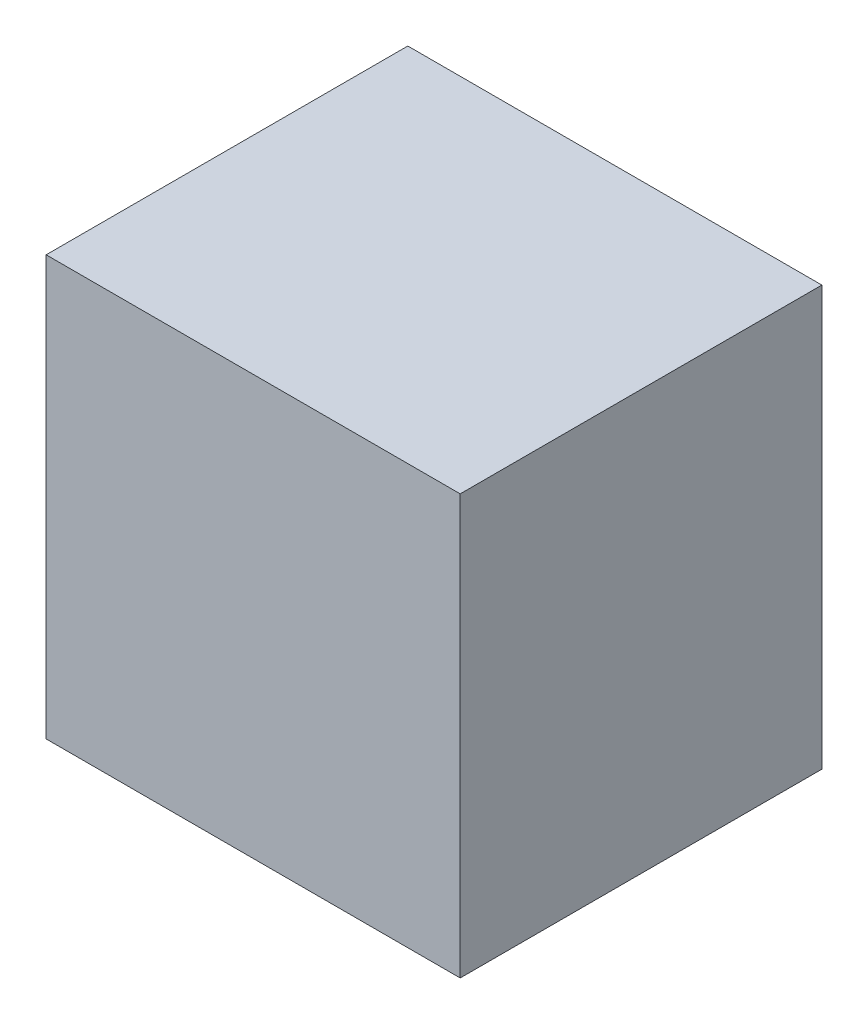
SolidWorks part; units mm, degrees
material "ABS"
ref_plane "Front Plane" through (0, 0, 0) normal (0, 0, 1) x (1, 0, 0)
ref_plane "Top Plane" through (0, 0, 0) normal (0, 1, 0) x (1, 0, 0)
ref_plane "Right Plane" through (0, 0, 0) normal (1, 0, 0) x (0, 0, -1)
sketch "Sketch1" plane through (0, 0, 0) normal (0, 1, 0) x (1, 0, 0)
  line L1 (3.95, -3.45) -> (-3.95, -3.45)
  line L2 (3.95, -3.45) -> (3.95, 3.45)
  line L3 (3.95, 3.45) -> (-3.95, 3.45)
  line L4 (-3.95, -3.45) -> (-3.95, 3.45)
  line L5 (3.95, -3.45) -> (-3.95, 3.45) construction
  line L6 (3.95, 3.45) -> (-3.95, -3.45) construction
  point P0 (0, 0)
  dimension "D1" = 6.9
  dimension "D2" = 7.9
extrude "Boss-Extrude1" add sketch "Sketch1" along normal blind 8
sketch "Sketch2" plane through (0, 0, -3.45) normal (0, 0, -1) x (-1, 0, 0)
  line L0 (-3.95, 8) -> (3.95, 8) construction
  line L1 (-2.5, 6.5) -> (2.5, 6.5)
  line L2 (-2.5, 6.5) -> (-2.5, 2.5)
  line L3 (-2.5, 2.5) -> (2.5, 2.5)
  line L4 (2.5, 6.5) -> (2.5, 2.5)
  line L5 (-2.5, 6.5) -> (2.5, 2.5) construction
  line L6 (-2.5, 2.5) -> (2.5, 6.5) construction
  point P0 (0, 4.5)
  dimension "D1" = 5
  dimension "D2" = 4
  dimension "D3" = 1.5
extrude "Cut-Extrude1" cut sketch "Sketch2" against normal blind 2
